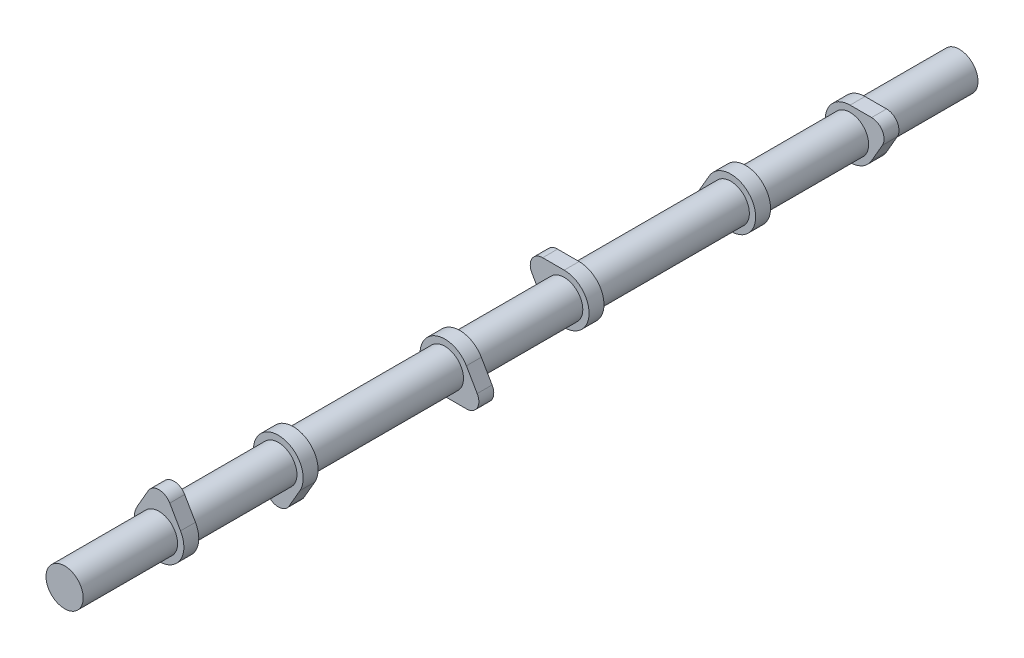
SolidWorks part; units mm, degrees
ref_plane "Front Plane" through (0, 0, 0) normal (0, 0, 1) x (1, 0, 0)
ref_plane "Top Plane" through (0, 0, 0) normal (0, 1, 0) x (1, 0, 0)
ref_plane "Right Plane" through (0, 0, 0) normal (1, 0, 0) x (0, 0, -1)
sketch "Sketch1" plane through (0, 0, 0) normal (0, 0, 1) x (1, 0, 0)
  line L0 (5.4993, 15.875) -> (10.9985, 6.35)
  line L1 (-5.4993, 15.875) -> (-10.9985, 6.35)
  arc A0 (-10.9985, 6.35) -> (10.9985, 6.35) centre (0, 0) ccw
  arc A1 (5.4993, 15.875) -> (-5.4993, 15.875) centre (0, 12.7) ccw
  point P1 (0.5796, 24.396)
  dimension "D1" = 25.4
  dimension "D3" = 12.7
  dimension "D2" = 12.7
extrude "Boss-Extrude1" add sketch "Sketch1" along normal mid plane 7.62
ref_axis "Axis1" through (0, 0, 471.3127) along (0, 0, -1)
pattern_linear "LPattern1" count 2 spacing 60.94 along (0, 0, 1) of bodies 101
pattern_linear "LPattern2" count 2 spacing 85.06 along (0, 0, 1) of bodies 102
pattern_linear "LPattern3" count 2 spacing 60.94 along (0, 0, 1) of bodies 103
pattern_linear "LPattern5" count 2 spacing 85.06 along (0, 0, 1) of bodies 104
pattern_linear "LPattern6" count 2 spacing 60.94 along (0, 0, 1) of bodies 107
ref_plane "Plane3" through (0, 0, 176.47) normal (0, 0, -1) x (-1, 0, 0)
move or copy body "Body-Move/Copy1" bodies to move or copy 107 103 101 copy no rotation origin (0, 0, 0) rotation axis (0, 0, 1) rotation angle 180
move or copy body "Body-Move/Copy2" bodies to move or copy 104 111 copy no rotation origin (0, 0, 0) rotation axis (0, 0, -1) rotation angle 120
move or copy body "Body-Move/Copy3" bodies to move or copy 102 112 copy no rotation origin (0, 0, 0) rotation axis (0, 0, 1) rotation angle 120
sketch "Sketch2" plane through (0, 0, 176.47) normal (0, 0, -1) x (-1, 0, 0)
  circle A0 centre (0, 0) radius 9.5
  dimension "D1" = 19
extrude "Boss-Extrude2" add sketch "Sketch2" along normal mid plane 456.98
